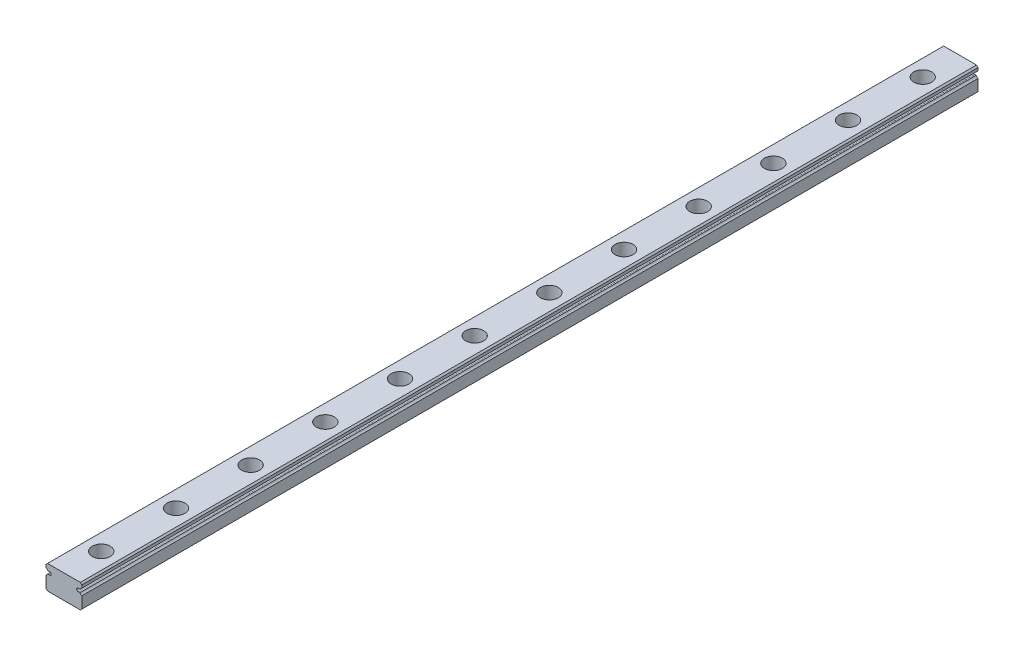
SolidWorks part; units mm, degrees
material "Chrome Stainless Steel"
ref_plane "Front Plane" through (0, 0, 0) normal (0, 0, 1) x (1, 0, 0)
ref_plane "Top Plane" through (0, 0, 0) normal (0, 1, 0) x (1, 0, 0)
ref_plane "Right Plane" through (0, 0, 0) normal (1, 0, 0) x (0, 0, -1)
sketch "Sketch1" plane through (0, 0, 0) normal (0, 0, 1) x (1, 0, 0)
  line L0 (0, 4) -> (0, -4) construction
  line L1 (5.5, -4) -> (-5.5, -4)
  line L2 (-5.5, -4) -> (-6, -3.5)
  line L3 (-6, -3.5) -> (-6, 0.3689)
  line L4 (5.5, 4) -> (-5.5, 4)
  line L5 (-5.5, 4) -> (-6, 3.5)
  line L6 (-6, 2.5511) -> (-6, 3.5)
  line L7 (-5.3839, 0.985) -> (-4.9211, 0.985)
  line L8 (-5.3839, 1.935) -> (-4.9211, 1.935)
  line L9 (5.3839, 0.985) -> (4.9211, 0.985)
  line L10 (5.5, 4) -> (6, 3.5)
  line L11 (6, 2.5511) -> (6, 3.5)
  line L12 (5.3839, 1.935) -> (4.9211, 1.935)
  line L13 (6, -3.5) -> (6, 0.3689)
  line L14 (5.5, -4) -> (6, -3.5)
  circle A0 centre (-6.475, 1.46) radius 1.19 construction
  circle A1 centre (-4.765, 1.46) radius 0.5 construction
  arc A2 (-6, 0.3689) -> (-5.3839, 0.985) centre (-6.475, 1.46) ccw
  arc A3 (-5.3839, 1.935) -> (-6, 2.5511) centre (-6.475, 1.46) ccw
  arc A4 (-4.9211, 0.985) -> (-4.9211, 1.935) centre (-4.765, 1.46) ccw
  arc A5 (5.3839, 1.935) -> (6, 2.5511) centre (6.475, 1.46) cw
  arc A6 (4.9211, 0.985) -> (4.9211, 1.935) centre (4.765, 1.46) cw
  arc A7 (6, 0.3689) -> (5.3839, 0.985) centre (6.475, 1.46) cw
  point P4 (0, 0)
  dimension "D5" = 5.46
  dimension "D6" = 6.475
  dimension "D7" = 2.38
  dimension "D11" = 1
  dimension "D12" = 5.46
  dimension "D13" = 4.765
  dimension "D1" = 8
  dimension "D2" = 0.5
  dimension "D3" = 0.5
  dimension "D4" = 6
  dimension "D8" = 0.5
  dimension "D9" = 0.5
  dimension "D10" = 6
  dimension "D14" = 0.475
  dimension "D15" = 0.475
extrude "Boss-Extrude1" add sketch "Sketch1" along normal blind 300 contours L13 A7 L9 A6 L12 A5 L11 L10 L4 L5 L6 A3 L8 A4 L7 A2 L3 L2 L1 L14 region at (0, -0.0654, 0)
sketch "Sketch2" plane through (0, 4, 0) normal (0, 1, 0) x (1, 0, 0)
  line L0 (5.5, 0) -> (-5.5, 0) construction
  circle A0 centre (0, -12.5) radius 3
  dimension "D1" = 12.5
extrude "Cut-Extrude1" cut sketch "Sketch2" against normal blind 4.5
sketch "Sketch3" plane through (0, -0.5, 0) normal (0, 1, 0) x (1, 0, 0)
  circle A0 centre (0, -12.5) radius 1.75
extrude "Cut-Extrude2" cut sketch "Sketch3" against normal through all
pattern_linear "LPattern1" count 14 spacing 25 along (0, 0, 1) of "Cut-Extrude1", "Cut-Extrude2"
ref_axis "Axis1" through (0, -0.5, 12.5) along (0, 1, 0)
ref_plane "Plane1" through (0, 0, 0) normal (-1, 0, 0) x (0, 1, 0)
